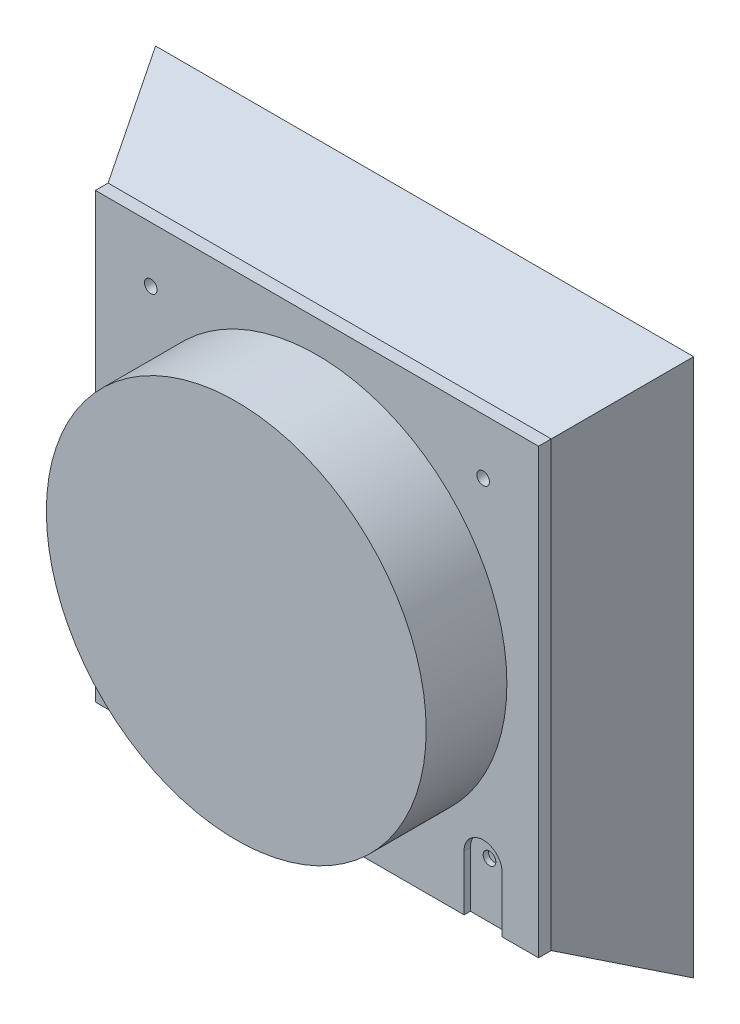
SolidWorks part; units mm, degrees
ref_plane "Front Plane" through (0, 0, 0) normal (0, 0, 1) x (1, 0, 0)
ref_plane "Top Plane" through (0, 0, 0) normal (0, 1, 0) x (1, 0, 0)
ref_plane "Right Plane" through (0, 0, 0) normal (1, 0, 0) x (0, 0, -1)
sketch "Sketch1" plane through (0, 0, 0) normal (0, 0, 1) x (1, 0, 0)
  line L0 (0, -70) -> (0, 70) construction
  line L1 (52.5, -52.5) -> (-52.5, -52.5) construction
  line L2 (52.5, -52.5) -> (52.5, 52.5) construction
  line L3 (52.5, 52.5) -> (-52.5, 52.5) construction
  line L4 (-52.5, -52.5) -> (-52.5, 52.5) construction
  line L5 (52.5, -52.5) -> (-52.5, 52.5) construction
  line L6 (52.5, 52.5) -> (-52.5, -52.5) construction
  line L7 (-70, -70) -> (70, -70)
  line L8 (-70, -70) -> (-70, 70)
  line L9 (-70, 70) -> (70, 70)
  line L10 (70, -70) -> (70, 70)
  line L11 (-70, -70) -> (70, 70) construction
  line L12 (-70, 70) -> (70, -70) construction
  line L13 (-70, 0) -> (70, 0) construction
  circle A0 centre (52.5, 52.5) radius 2
  circle A1 centre (0, 0) radius 59
  circle A2 centre (-52.5, 52.5) radius 2
  circle A3 centre (52.5, -52.5) radius 2
  circle A4 centre (-52.5, -52.5) radius 2
  point P0 (0, 0)
  point P6 (0, 0)
  dimension "D5" = 4
  dimension "D6" = 118
  dimension "D1" = 105
  dimension "D2" = 105
  dimension "D3" = 140
  dimension "D4" = 140
extrude "Boss-Extrude1" add sketch "Sketch1" along normal blind 4
ref_plane "Plane1" through (0, 0, -30) normal (0, 0, -1) x (-1, 0, 0)
sketch "Sketch2" plane through (0, 0, -30) normal (0, 0, -1) x (-1, 0, 0)
  line L1 (85, -85) -> (-85, -85)
  line L2 (85, -85) -> (85, 85)
  line L3 (85, 85) -> (-85, 85)
  line L4 (-85, -85) -> (-85, 85)
  line L5 (85, -85) -> (-85, 85) construction
  line L6 (85, 85) -> (-85, -85) construction
  line L7 (83, -83) -> (-83, -83)
  line L8 (83, -83) -> (83, 83)
  line L9 (83, 83) -> (-83, 83)
  line L10 (-83, -83) -> (-83, 83)
  line L11 (83, -83) -> (-83, 83) construction
  line L12 (83, 83) -> (-83, -83) construction
  point P0 (0, 0)
  point P6 (0, 0)
  dimension "D1" = 170
  dimension "D2" = 166
sketch "Sketch3" plane through (0, 0, 0) normal (0, 0, -1) x (-1, 0, 0)
  line L1 (-70, 70) -> (70, 70)
  line L2 (-70, 70) -> (-70, -70)
  line L3 (-70, -70) -> (70, -70)
  line L4 (70, 70) -> (70, -70)
  line L5 (61, -61) -> (-61, -61)
  line L6 (61, -61) -> (61, 61)
  line L7 (61, 61) -> (-61, 61)
  line L8 (-61, -61) -> (-61, 61)
  line L9 (61, -61) -> (-61, 61) construction
  line L10 (61, 61) -> (-61, -61) construction
  point P6 (0, 0)
  dimension "D1" = 122
loft "Loft3" add section "Sketch2" section "Sketch3" connector at (-85, 85, -30) connector at (-70, 70, 0)
shell "Shell2" thickness 4 removed face at (59, 0, 0) removed face at (54.5, 52.5, 0) removed face at (-54.5, 52.5, 0) removed face at (50.5, -52.5, 0) removed face at (-50.5, -52.5, 0) removed face at (-42.5, -42.5, -30)
sketch "Sketch4" plane through (0, 0, 4) normal (0, 0, 1) x (1, 0, 0)
  circle A0 centre (0, 0) radius 60
  dimension "D1" = 120
extrude "Boss-Extrude3" add sketch "Sketch4" along normal blind 25.5 separate body
sketch "Sketch7" plane through (0, 0, 4) normal (0, 0, 1) x (1, 0, 0)
  line L0 (-58.525, -70) -> (-46.475, -70)
  line L1 (-70, -70) -> (70, -70) construction
  line L2 (-70, -70) -> (70, -70) construction
  line L3 (-46.475, -70) -> (-46.475, -52.5)
  line L4 (-58.525, -70) -> (-58.525, -52.5)
  line L5 (0, -18.7) -> (0, 18.7) construction
  line L6 (58.525, -70) -> (46.475, -70)
  line L7 (46.475, -70) -> (46.475, -52.5)
  line L8 (58.525, -70) -> (58.525, -52.5)
  circle A0 centre (52.5, -52.5) radius 2 construction
  circle A1 centre (-52.5, -52.5) radius 2 construction
  circle A2 centre (52.5, -52.5) radius 2 construction
  circle A3 centre (-52.5, -52.5) radius 2 construction
  arc A4 (-46.475, -52.5) -> (-58.525, -52.5) centre (-52.5, -52.5) ccw
  arc A5 (46.475, -52.5) -> (58.525, -52.5) centre (52.5, -52.5) cw
  dimension "D1" = 12.05
extrude "Cut-Extrude1" cut sketch "Sketch7" against normal blind 2
sketch "Sketch8" plane through (0, 0, 0) normal (0, 0, -1) x (-1, 0, 0)
  circle A0 centre (-52.5, -52.5) radius 2 construction
  circle A1 centre (52.5, -52.5) radius 2 construction
  circle A2 centre (52.5, 52.5) radius 2 construction
  circle A3 centre (-52.5, 52.5) radius 2 construction
  circle A4 centre (-52.5, -52.5) radius 2 construction
  circle A5 centre (52.5, -52.5) radius 2 construction
  circle A6 centre (52.5, 52.5) radius 2 construction
  circle A7 centre (-52.5, 52.5) radius 2 construction
  circle A8 centre (-52.5, 52.5) radius 3.9
  circle A9 centre (52.5, 52.5) radius 3.9
  circle A10 centre (52.5, -52.5) radius 3.9
  circle A11 centre (-52.5, -52.5) radius 3.9
  dimension "D1" = 1.9
extrude "Cut-Extrude2" cut sketch "Sketch8" against normal blind 0.3333
